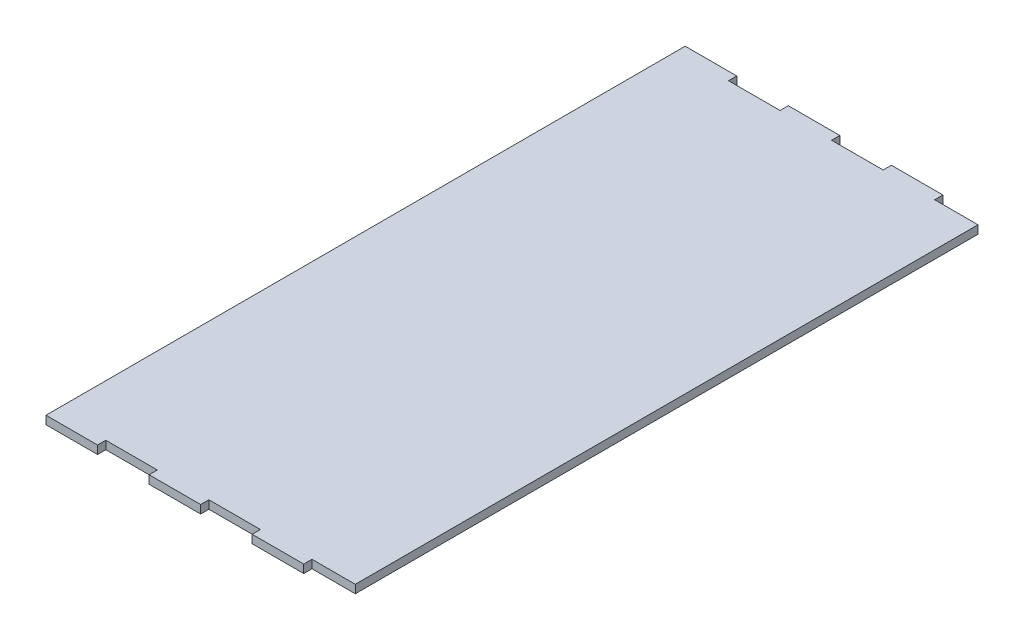
SolidWorks part; units mm, degrees
ref_plane "Alzado" through (0, 0, 0) normal (0, 0, 1) x (1, 0, 0)
ref_plane "Planta" through (0, 0, 0) normal (0, 1, 0) x (1, 0, 0)
ref_plane "Vista lateral" through (0, 0, 0) normal (1, 0, 0) x (0, 0, -1)
sketch "Croquis1" plane through (0, 0, 0) normal (0, 1, 0) x (1, 0, 0)
  line L0 (-100, 155) -> (-50, 155)
  line L1 (-200, 155) -> (200, 155) construction
  line L2 (-200, 155) -> (-200, -155) construction
  line L3 (-200, -155) -> (200, -155) construction
  line L4 (200, 155) -> (200, -155) construction
  line L5 (-200, 155) -> (200, -155) construction
  line L6 (-200, -155) -> (200, 155) construction
  line L7 (-200, -155) -> (-150, -155)
  line L8 (-200, -155) -> (-200, 155)
  line L9 (-200, 155) -> (-150, 155)
  line L10 (-50, -155) -> (-50, 155)
  line L11 (-150, -151) -> (-100, -151) construction
  line L12 (-150, -151) -> (-150, -155) construction
  line L13 (-150, -155) -> (-100, -155) construction
  line L14 (-100, -151) -> (-100, -155) construction
  line L15 (-150, 151) -> (-100, 151) construction
  line L16 (-150, 151) -> (-150, 155) construction
  line L17 (-150, 155) -> (-100, 155) construction
  line L18 (-100, 151) -> (-100, 155) construction
  line L19 (-150, 151) -> (-100, 155) construction
  line L20 (-150, 155) -> (-100, 151) construction
  line L21 (-200, 105) -> (-196, 105) construction
  line L22 (-200, 105) -> (-200, 55) construction
  line L23 (-200, 55) -> (-196, 55) construction
  line L24 (-196, 105) -> (-196, 55) construction
  line L25 (-200, 105) -> (-196, 55) construction
  line L26 (-200, 55) -> (-196, 105) construction
  line L27 (-200, -55) -> (-196, -55) construction
  line L28 (-200, -55) -> (-200, -105) construction
  line L29 (-200, -105) -> (-196, -105) construction
  line L30 (-196, -55) -> (-196, -105) construction
  line L31 (-200, -55) -> (-196, -105) construction
  line L32 (-200, -105) -> (-196, -55) construction
  line L33 (-100, -155) -> (-50, -155)
  line L34 (-196, 155) -> (-196, -155)
  line L35 (-150, 155) -> (-100, 155)
  line L36 (-150, -155) -> (-100, -155)
  point P0 (0, 0)
  point P16 (-125, 153)
  point P21 (-198, 80)
  point P26 (-198, -80)
  point P30 (-196, -105)
  dimension "D1" = 310
  dimension "D2" = 400
  dimension "D3" = 150
  dimension "D4" = 50
  dimension "D5" = 50
  dimension "D6" = 50
  dimension "D7" = 50
  dimension "D8" = 50
  dimension "D9" = 4
extrude "Saliente-Extruir1" add sketch "Croquis1" along normal blind 4 contours L9 L34 L7 L12 L11 L14 L33 L10 L0 L18 L15 L16 region at (-123, 0, 0)
sketch "Croquis2" plane through (0, 4, 0) normal (0, 1, 0) x (1, 0, 0)
  line L0 (-196, 155) -> (-171, 155)
  line L1 (-196, 155) -> (-50, 155) construction
  line L2 (-171, 155) -> (-171, 151)
  line L3 (-171, 151) -> (-146, 151)
  line L4 (-146, 151) -> (-146, 155)
  line L5 (-146, 155) -> (-121, 155)
  line L6 (-121, 155) -> (-121, 151)
  line L7 (-121, 151) -> (-96, 151)
  line L8 (-96, 151) -> (-96, 155)
  line L9 (-96, 155) -> (-71, 155)
  line L10 (-71, 155) -> (-71, 151)
  line L11 (-71, 151) -> (-46, 151)
  line L12 (-46, 151) -> (-46, 195.5944)
  line L13 (-46, 195.5944) -> (-196, 195.5944)
  line L14 (-196, 195.5944) -> (-196, 155)
  line L15 (-2.2, 0) -> (2.2, 0) construction
  line L16 (-196, -195.5944) -> (-196, -155)
  line L17 (-46, -195.5944) -> (-196, -195.5944)
  line L18 (-46, -151) -> (-46, -195.5944)
  line L19 (-71, -151) -> (-46, -151)
  line L20 (-71, -155) -> (-71, -151)
  line L21 (-96, -155) -> (-71, -155)
  line L22 (-96, -151) -> (-96, -155)
  line L23 (-121, -151) -> (-96, -151)
  line L24 (-121, -155) -> (-121, -151)
  line L25 (-146, -155) -> (-121, -155)
  line L26 (-146, -151) -> (-146, -155)
  line L27 (-171, -151) -> (-146, -151)
  line L28 (-171, -155) -> (-171, -151)
  line L29 (-196, -155) -> (-171, -155)
  dimension "D1" = 25
  dimension "D2" = 4
extrude "Cortar-Extruir1" cut sketch "Croquis2" against normal blind 10
equation "\"D2@Croquis1\" = \"largo_tot\""
equation "\"D3@Croquis1\"=150"
equation "\"D1@Croquis1\" = \"ancho_tot\""
equation "\"venesta\"= 4'grosor de la venesta"
equation "\"policarbonato\"= 4'grosor del policarbonato"
equation "\"carton_trupan\"= 3'grosor del carton trupan caso laser"
equation "\"ancho_tot\"= 310'ancho tot sin llantas"
equation "\"largo_tot\"= 400'largo tot sin camera"
equation "\"D1@Saliente-Extruir1\"=\"policarbonato\""
equation "\"D9@Croquis1\"=\"policarbonato\""
equation "\"D2@Croquis2\"=\"policarbonato\""
